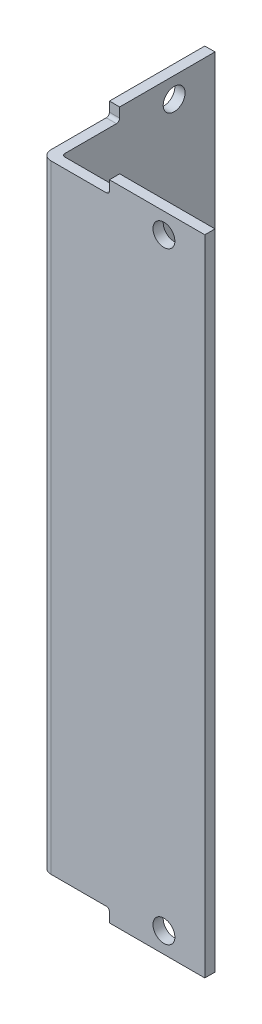
SolidWorks part; units mm, degrees
material "6061-T6 (SS)"
ref_plane "Front Plane" through (0, 0, 0) normal (0, 0, 1) x (1, 0, 0)
ref_plane "Top Plane" through (0, 0, 0) normal (0, 1, 0) x (1, 0, 0)
ref_plane "Right Plane" through (0, 0, 0) normal (1, 0, 0) x (0, 0, -1)
sketch "Sketch1" plane through (0, 0, 0) normal (0, 1, 0) x (1, 0, 0)
  line L1 (-12.7, -12.7) -> (12.7, -12.7)
  line L2 (-12.7, -12.7) -> (-12.7, 12.7)
  line L3 (-12.7, 12.7) -> (12.7, 12.7)
  line L4 (12.7, -12.7) -> (12.7, 12.7)
  line L5 (-12.7, -12.7) -> (12.7, 12.7) construction
  line L6 (-12.7, 12.7) -> (12.7, -12.7) construction
  point P0 (0, 0)
  dimension "D1" = 25.4
  dimension "D2" = 25.4
extrude "Boss-Extrude1" add sketch "Sketch1" along normal mid plane 113.5
sketch "Sketch2" plane through (0, 56.75, 0) normal (0, 1, 0) x (1, 0, 0)
  line L0 (-12.7, 12.7) -> (-12.7, -12.7) construction
  line L1 (12.7, 12.7) -> (-11.1125, 12.7)
  line L2 (12.7, 12.7) -> (12.7, -11.1125)
  line L3 (12.7, -11.1125) -> (-11.1125, -11.1125)
  line L4 (-11.1125, 12.7) -> (-11.1125, -11.1125)
  line L5 (-12.7, -12.7) -> (12.7, -12.7) construction
  dimension "D1" = 1.5875
  dimension "D2" = 1.5875
extrude "Cut-Extrude1" cut sketch "Sketch2" against normal through all
fillet "Fillet1" radius 0.508 1 edges at (-11.1125, 0, 11.1125)
hole_wizard "M3 Clearance Hole1" positions "Sketch3" profile "Sketch4" hole size "M3" standard "ANSI Metric" end condition through all
sketch "Sketch3" plane through (0, 0, 12.7) normal (0, 0, 1) x (1, 0, 0)
  line L1 (-12.7, 56.75) -> (12.7, 56.75) construction
  line L2 (12.7, 56.75) -> (12.7, -56.75) construction
  point P0 (6.35, 47.075)
  dimension "D1" = 6.35
  dimension "D2" = 9.675
sketch "Sketch4" plane through (6.35, 47.075, 12.7) normal (1, 0, 0) x (0, -1, 0)
  line L0 (0, 0) -> (0, 25.4)
  line L1 (0, 25.4) -> (1.7, 25.4)
  line L2 (1.7, 25.4) -> (1.7, 0)
  line L5 (1.7, 0) -> (0, 0)
  line L11 (0, -6.35) -> (0, 107.95) construction
  dimension "Thru Hole Dia." = 3.4
  dimension "Thru Hole Depth" = 25.4
hole_wizard "M3 Clearance Hole2" positions "Sketch5" profile "Sketch6" hole size "M3" standard "ANSI Metric" end condition through all
sketch "Sketch5" plane through (-12.7, 0, 0) normal (-1, 0, 0) x (0, 0, 1)
  line L1 (-12.7, 56.75) -> (12.7, 56.75) construction
  line L2 (-12.7, 56.75) -> (-12.7, -56.75) construction
  point P0 (-6.35, 47.075)
  dimension "D1" = 6.35
  dimension "D2" = 9.675
sketch "Sketch6" plane through (-12.7, 47.075, -6.35) normal (0, 1, 0) x (0, 0, 1)
  line L0 (0, 0) -> (0, 25.4)
  line L1 (0, 25.4) -> (1.7, 25.4)
  line L2 (1.7, 25.4) -> (1.7, 0)
  line L5 (1.7, 0) -> (0, 0)
  line L11 (0, -6.35) -> (0, 107.95) construction
  dimension "Thru Hole Dia." = 3.4
  dimension "Thru Hole Depth" = 25.4
hole_wizard "M3 Clearance Hole3" positions "Sketch7" profile "Sketch8" hole size "M3" standard "ANSI Metric" end condition through all
sketch "Sketch7" plane through (0, 0, 12.7) normal (0, 0, 1) x (1, 0, 0)
  line L2 (-12.7, -56.75) -> (12.7, -56.75) construction
  line L3 (12.7, 56.75) -> (12.7, -56.75) construction
  point P0 (6.35, -46.575)
  dimension "D1" = 6.35
  dimension "D2" = 10.175
sketch "Sketch8" plane through (6.35, -46.575, 12.7) normal (1, 0, 0) x (0, -1, 0)
  line L0 (0, 0) -> (0, 25.4)
  line L1 (0, 25.4) -> (1.7, 25.4)
  line L2 (1.7, 25.4) -> (1.7, 0)
  line L5 (1.7, 0) -> (0, 0)
  line L11 (0, -6.35) -> (0, 107.95) construction
  dimension "Thru Hole Dia." = 3.4
  dimension "Thru Hole Depth" = 25.4
hole_wizard "M3 Clearance Hole4" positions "Sketch9" profile "Sketch10" hole size "M3" standard "ANSI Metric" end condition through all
sketch "Sketch9" plane through (-12.7, 0, 0) normal (-1, 0, 0) x (0, 0, 1)
  line L1 (-12.7, -56.75) -> (12.7, -56.75) construction
  line L2 (-12.7, 56.75) -> (-12.7, -56.75) construction
  point P0 (-6.35, -46.575)
  dimension "D1" = 6.35
  dimension "D2" = 10.175
sketch "Sketch10" plane through (-12.7, -46.575, -6.35) normal (0, 1, 0) x (0, 0, 1)
  line L0 (0, 0) -> (0, 25.4)
  line L1 (0, 25.4) -> (1.7, 25.4)
  line L2 (1.7, 25.4) -> (1.7, 0)
  line L5 (1.7, 0) -> (0, 0)
  line L11 (0, -6.35) -> (0, 107.95) construction
  dimension "Thru Hole Dia." = 3.4
  dimension "Thru Hole Depth" = 25.4
fillet "Fillet2" radius 1.5 1 edges at (-12.7, 0, 12.7)
sketch "Sketch11" plane through (-12.7, 0, 0) normal (-1, 0, 0) x (0, 0, 1)
  line L0 (12.7, 56.75) -> (12.7, -56.75) construction
  line L1 (-12.7, 56.75) -> (4.2, 56.75)
  line L2 (-12.7, 56.75) -> (-12.7, 50.25)
  line L3 (-12.7, 50.25) -> (4.2, 50.25)
  line L4 (4.2, 56.75) -> (4.2, 50.25)
  line L6 (-12.7, -56.75) -> (4.2, -56.75)
  line L7 (-12.7, -56.75) -> (-12.7, -49.75)
  line L8 (-12.7, -49.75) -> (4.2, -49.75)
  line L9 (4.2, -56.75) -> (4.2, -49.75)
  dimension "D1" = 8.5
  dimension "D2" = 6.5
  dimension "D3" = 7
extrude "Cut-Extrude2" cut sketch "Sketch11" against normal up to next
sketch "Sketch12" plane through (0, 0, 12.7) normal (0, 0, 1) x (1, 0, 0)
  line L0 (-12.7, -56.75) -> (-12.7, 56.75) construction
  line L1 (12.7, 56.75) -> (-4.2, 56.75)
  line L2 (12.7, 56.75) -> (12.7, 50.25)
  line L3 (12.7, 50.25) -> (-4.2, 50.25)
  line L4 (-4.2, 56.75) -> (-4.2, 50.25)
  line L5 (12.7, -56.75) -> (-4.2, -56.75)
  line L6 (12.7, -56.75) -> (12.7, -49.75)
  line L7 (12.7, -49.75) -> (-4.2, -49.75)
  line L8 (-4.2, -56.75) -> (-4.2, -49.75)
  dimension "D1" = 8.5
  dimension "D2" = 7
  dimension "D3" = 8.5
  dimension "D4" = 6.5
extrude "Cut-Extrude3" cut sketch "Sketch12" against normal up to next
fillet "Fillet3" radius 3.81 4 edges at (-4.2, -49.75, 11.9062) (-11.9063, -49.75, 4.2) (-11.9063, 50.25, 4.2) (-4.2, 50.25, 11.9062)
sketch "Sketch13" plane through (-12.7, 0, 0) normal (-1, 0, 0) x (0, 0, 1)
  line L0 (4.2, -56.75) -> (4.2, 56.75) construction
  line L9 (2.7, -56.75) -> (2.7, 56.75) construction
  line L10 (-12.7, 50.25) -> (-12.7, -49.75) construction
  line L11 (2.7, -43.4) -> (-12.7, -43.4)
  line L12 (2.7, -43.4) -> (2.7, 43.9)
  line L13 (2.7, 43.9) -> (-12.7, 43.9)
  line L14 (-12.7, -43.4) -> (-12.7, 43.9)
  circle A2 centre (-6.35, 47.075) radius 1.7 construction
  circle A3 centre (-6.35, -46.575) radius 1.7 construction
  dimension "D2" = 3.175
  dimension "D3" = 3.175
  dimension "D1" = 1.5
extrude "Cut-Extrude4" cut sketch "Sketch13" against normal up to next
sketch "Sketch14" plane through (0, 0, 12.7) normal (0, 0, 1) x (1, 0, 0)
  line L0 (-4.2, 56.75) -> (-4.2, -56.75) construction
  line L1 (-2.7, 56.75) -> (-2.7, -56.75) construction
  line L2 (12.7, 50.25) -> (12.7, -49.75) construction
  line L3 (-2.7, -43.4) -> (12.7, -43.4)
  line L4 (-2.7, -43.4) -> (-2.7, 43.9)
  line L5 (-2.7, 43.9) -> (12.7, 43.9)
  line L6 (12.7, -43.4) -> (12.7, 43.9)
  circle A0 centre (6.35, 47.075) radius 1.7 construction
  circle A1 centre (6.35, -46.575) radius 1.7 construction
  dimension "D2" = 3.175
  dimension "D3" = 3.175
  dimension "D1" = 1.5
extrude "Cut-Extrude5" cut sketch "Sketch14" against normal up to next
chamfer "Chamfer2" distance 6.35 angle 45 4 edges at (-11.9063, 43.9, 2.7) (-2.7, 43.9, 11.9062) (-2.7, -43.4, 11.9062) (-11.9062, -43.4, 2.7)
fillet "Fillet5" radius 3.81 8 edges at (3.65, -43.4, 11.9062) (-2.7, -37.05, 11.9062) (-11.9063, -43.4, -3.65) (-11.9063, -37.05, 2.7) (-11.9063, 43.9, -3.65) (-11.9063, 37.55, 2.7) (-2.7, 37.55, 11.9062) (3.65, 43.9, 11.9062)
sketch "Sketch15" plane through (0, 56.75, 0) normal (0, 1, 0) x (1, 0, 0)
  line L0 (-11.2, -12.7) -> (-4.2, -12.7) construction
  line L1 (-12.7, -12.7) -> (-0.39, -12.7)
  line L2 (-12.7, -12.7) -> (-12.7, -0.39)
  line L3 (-12.7, -0.39) -> (-0.39, -0.39)
  line L4 (-0.39, -12.7) -> (-0.39, -0.39)
  line L5 (-12.7, -4.2) -> (-12.7, -11.2) construction
  line L6 (-0.39, -11.1125) -> (-0.39, -12.7) construction
extrude "Cut-Extrude6" cut sketch "Sketch15" against normal up to surface (6.5 mm away) up to face at (6.155, 50.25, 11.9062)
sketch "Sketch16" plane through (0, 50.25, 0) normal (0, 1, 0) x (1, 0, 0)
  line L0 (-11.2, -12.7) -> (12.7, -12.7) construction
  line L1 (-12.7, -12.7) -> (-5.7, -12.7)
  line L2 (-12.7, -12.7) -> (-12.7, -5.7)
  line L3 (-12.7, -5.7) -> (-5.7, -5.7)
  line L4 (-5.7, -12.7) -> (-5.7, -5.7)
  line L5 (-12.7, 12.7) -> (-12.7, -11.2) construction
  dimension "D1" = 7
  dimension "D2" = 7
sketch "Sketch17" plane through (0, -56.75, 0) normal (0, -1, 0) x (1, 0, 0)
  line L0 (-11.2, 12.7) -> (-4.2, 12.7) construction
  line L1 (-12.7, 12.7) -> (-0.39, 12.7)
  line L2 (-12.7, 12.7) -> (-12.7, 0.39)
  line L3 (-12.7, 0.39) -> (-0.39, 0.39)
  line L4 (-0.39, 12.7) -> (-0.39, 0.39)
  line L5 (-12.7, 4.2) -> (-12.7, 11.2) construction
  line L6 (-11.1125, 0.39) -> (-12.7, 0.39) construction
  line L7 (-0.39, 12.7) -> (-0.39, 11.1125) construction
extrude "Cut-Extrude8" cut sketch "Sketch17" against normal up to surface (7 mm away) up to face at (6.155, -49.75, 11.9062)
sketch "Sketch18" plane through (-12.7, 0, 0) normal (-1, 0, 0) x (0, 0, 1)
  line L0 (-12.7, -43.4) -> (-5.2282, -43.4) construction
  line L1 (5.7, -43.4) -> (11.2, -43.4)
  line L2 (5.7, -43.4) -> (5.7, -40.4)
  line L3 (5.7, -40.4) -> (11.2, -40.4)
  line L4 (11.2, -43.4) -> (11.2, -40.4)
  line L5 (12.7, 50.25) -> (12.7, -49.75) construction
  point P8 (8.45, -40.4)
  dimension "D1" = 5.5
  dimension "D2" = 3
  dimension "D3" = 4.25
sketch "Sketch19" plane through (0, -49.75, 0) normal (0, -1, 0) x (1, 0, 0)
  line L0 (12.7, 12.7) -> (-11.2, 12.7) construction
  line L1 (-12.7, 5.7) -> (-5.7, 5.7)
  line L2 (-12.7, 5.7) -> (-12.7, 12.7)
  line L3 (-12.7, 12.7) -> (-5.7, 12.7)
  line L4 (-5.7, 5.7) -> (-5.7, 12.7)
  line L5 (-12.7, 11.2) -> (-12.7, -12.7) construction
sketch "Sketch20" plane through (-12.7, 0, 0) normal (-1, 0, 0) x (0, 0, 1)
  line L0 (-12.7, 43.9) -> (-12.7, -43.4)
  line L13 (7.2, -40.4) -> (11.2, -40.4)
  line L14 (11.2, -40.4) -> (11.2, 50.25)
  line L15 (11.2, 50.25) -> (-12.7, 50.25)
  line L16 (-12.7, 50.25) -> (-12.7, 43.9)
  line L17 (-12.7, 43.9) -> (-5.2282, 43.9)
  line L18 (-2.5341, 42.7841) -> (1.5841, 38.6659)
  line L19 (2.7, 35.9718) -> (2.7, -35.4718)
  line L20 (1.5841, -38.1659) -> (-2.5341, -42.2841)
  line L21 (-5.2282, -43.4) -> (-12.7, -43.4)
  line L22 (-12.7, -43.4) -> (-12.7, -49.75)
  line L23 (-12.7, -49.75) -> (11.2, -49.75)
  line L24 (11.2, -49.75) -> (11.2, -43.4)
  line L25 (11.2, -43.4) -> (7.2, -43.4)
  line L26 (7.2, -40.4) -> (11.2, -40.4)
  line L27 (11.2, -40.4) -> (11.2, 50.25)
  line L28 (11.2, 50.25) -> (-12.7, 50.25)
  line L29 (-12.7, 50.25) -> (-12.7, 43.9)
  line L30 (-12.7, 43.9) -> (-5.2282, 43.9)
  line L31 (-2.5341, 42.7841) -> (1.5841, 38.6659)
  line L32 (2.7, 35.9718) -> (2.7, -35.4718)
  line L33 (1.5841, -38.1659) -> (-2.5341, -42.2841)
  line L34 (-5.2282, -43.4) -> (-12.7, -43.4)
  line L35 (-12.7, -43.4) -> (-12.7, -49.75)
  line L36 (-12.7, -49.75) -> (11.2, -49.75)
  line L37 (11.2, -49.75) -> (11.2, -43.4)
  line L38 (11.2, -43.4) -> (7.2, -43.4)
  arc A5 (7.2, -40.4) -> (7.2, -43.4) centre (7.2, -41.9) ccw
  arc A6 (-2.5341, 42.7841) -> (-5.2282, 43.9) centre (-5.2282, 40.09) ccw
  arc A7 (2.7, 35.9718) -> (1.5841, 38.6659) centre (-1.11, 35.9718) ccw
  arc A8 (1.5841, -38.1659) -> (2.7, -35.4718) centre (-1.11, -35.4718) ccw
  arc A9 (-5.2282, -43.4) -> (-2.5341, -42.2841) centre (-5.2282, -39.59) ccw
  arc A10 (7.2, -40.4) -> (7.2, -43.4) centre (7.2, -41.9) ccw
  arc A11 (-2.5341, 42.7841) -> (-5.2282, 43.9) centre (-5.2282, 40.09) ccw
  arc A12 (2.7, 35.9718) -> (1.5841, 38.6659) centre (-1.11, 35.9718) ccw
  arc A13 (1.5841, -38.1659) -> (2.7, -35.4718) centre (-1.11, -35.4718) ccw
  arc A14 (-5.2282, -43.4) -> (-2.5341, -42.2841) centre (-5.2282, -39.59) ccw
  line M26 (-12.7, 43.9) -> (-5.2282, 43.9)
  arc M27 (-5.2282, 43.9) -> (-2.5341, 42.7841) centre (-5.2282, 40.09) cw
  line M28 (-2.5341, 42.7841) -> (1.5841, 38.6659)
  arc M29 (1.5841, 38.6659) -> (2.7, 35.9718) centre (-1.11, 35.9718) cw
  line M30 (2.7, 35.9718) -> (2.7, -35.4718)
  arc M31 (2.7, -35.4718) -> (1.5841, -38.1659) centre (-1.11, -35.4718) cw
  line M32 (1.5841, -38.1659) -> (-2.5341, -42.2841)
  arc M33 (-2.5341, -42.2841) -> (-5.2282, -43.4) centre (-5.2282, -39.59) cw
  line M34 (-5.2282, -43.4) -> (-12.7, -43.4)
  dimension "D1" = 0
extrude "Boss-Extrude2" add sketch "Sketch20" against normal up to surface (1.5875 mm away) contours L0 M26 M34 M33 M32 M31 M30 M29 M28 M27 region at (-12.7, 0.25, -5.177) up to face at (-11.1125, -46.575, -4.65)
sketch "Sketch21" plane through (0, 0, 12.7) normal (0, 0, 1) x (1, 0, 0)
  line L0 (12.7, 43.9) -> (12.7, -43.4)
  line L14 (-11.2, 50.25) -> (-11.2, -49.75)
  line L15 (-11.2, -49.75) -> (12.7, -49.75)
  line L16 (12.7, -49.75) -> (12.7, -43.4)
  line L17 (12.7, -43.4) -> (5.2282, -43.4)
  line L18 (2.5341, -42.2841) -> (-1.5841, -38.1659)
  line L19 (-2.7, -35.4718) -> (-2.7, 35.9718)
  line L20 (-1.5841, 38.6659) -> (2.5341, 42.7841)
  line L21 (5.2282, 43.9) -> (12.7, 43.9)
  line L22 (12.7, 43.9) -> (12.7, 50.25)
  line L23 (12.7, 50.25) -> (-11.2, 50.25)
  line L27 (-11.2, 50.25) -> (-11.2, -49.75)
  line L28 (-11.2, -49.75) -> (12.7, -49.75)
  line L29 (12.7, -49.75) -> (12.7, -43.4)
  line L30 (12.7, -43.4) -> (5.2282, -43.4)
  line L31 (2.5341, -42.2841) -> (-1.5841, -38.1659)
  line L32 (-2.7, -35.4718) -> (-2.7, 35.9718)
  line L33 (-1.5841, 38.6659) -> (2.5341, 42.7841)
  line L34 (5.2282, 43.9) -> (12.7, 43.9)
  line L35 (12.7, 43.9) -> (12.7, 50.25)
  line L36 (12.7, 50.25) -> (-11.2, 50.25)
  arc A6 (2.5341, -42.2841) -> (5.2282, -43.4) centre (5.2282, -39.59) ccw
  arc A7 (-2.7, -35.4718) -> (-1.5841, -38.1659) centre (1.11, -35.4718) ccw
  arc A8 (-1.5841, 38.6659) -> (-2.7, 35.9718) centre (1.11, 35.9718) ccw
  arc A9 (5.2282, 43.9) -> (2.5341, 42.7841) centre (5.2282, 40.09) ccw
  arc A11 (2.5341, -42.2841) -> (5.2282, -43.4) centre (5.2282, -39.59) ccw
  arc A12 (-2.7, -35.4718) -> (-1.5841, -38.1659) centre (1.11, -35.4718) ccw
  arc A13 (-1.5841, 38.6659) -> (-2.7, 35.9718) centre (1.11, 35.9718) ccw
  arc A14 (5.2282, 43.9) -> (2.5341, 42.7841) centre (5.2282, 40.09) ccw
  line M24 (12.7, -43.4) -> (5.2282, -43.4)
  arc M25 (5.2282, -43.4) -> (2.5341, -42.2841) centre (5.2282, -39.59) cw
  line M26 (2.5341, -42.2841) -> (-1.5841, -38.1659)
  arc M27 (-1.5841, -38.1659) -> (-2.7, -35.4718) centre (1.11, -35.4718) cw
  line M28 (-2.7, -35.4718) -> (-2.7, 35.9718)
  arc M29 (-2.7, 35.9718) -> (-1.5841, 38.6659) centre (1.11, 35.9718) cw
  line M30 (-1.5841, 38.6659) -> (2.5341, 42.7841)
  arc M31 (2.5341, 42.7841) -> (5.2282, 43.9) centre (5.2282, 40.09) cw
  line M32 (5.2282, 43.9) -> (12.7, 43.9)
  dimension "D1" = 0
sketch "Sketch22" plane through (0, 50.25, 0) normal (0, 1, 0) x (1, 0, 0)
  line L0 (-12.7, 12.7) -> (-12.7, -11.2) construction
  line L1 (-12.7, -12.7) -> (-2.1125, -12.7)
  line L2 (-12.7, -12.7) -> (-12.7, -2.1125)
  line L3 (-12.7, -2.1125) -> (-2.1125, -2.1125)
  line L4 (-2.1125, -12.7) -> (-2.1125, -2.1125)
  line L5 (12.7, -12.7) -> (-11.2, -12.7) construction
  line L6 (12.7, -11.1125) -> (-10.6045, -11.1125) construction
  dimension "D1" = 9
extrude "Boss-Extrude3" add sketch "Sketch21" against normal up to surface (1.5875 mm away) contours L0 M32 M31 M30 M29 M28 M27 M26 M25 M24 region at (5.177, 0.25, 12.7) up to face at (8.05, -46.575, 11.1125)
extrude "Cut-Extrude9" cut sketch "Sketch22" against normal blind 2
fillet "Fillet6" radius 0.5 2 edges at (-2.1125, 48.25, 11.9062) (-11.9063, 48.25, 2.1125)
ref_plane "Plane1" through (0, 0.25, 0) normal (0, 1, 0) x (1, 0, 0)
mirror "Mirror1" about plane through (0, 0.25, 0) normal (0, 1, 0) of "Cut-Extrude9", "Fillet6"
